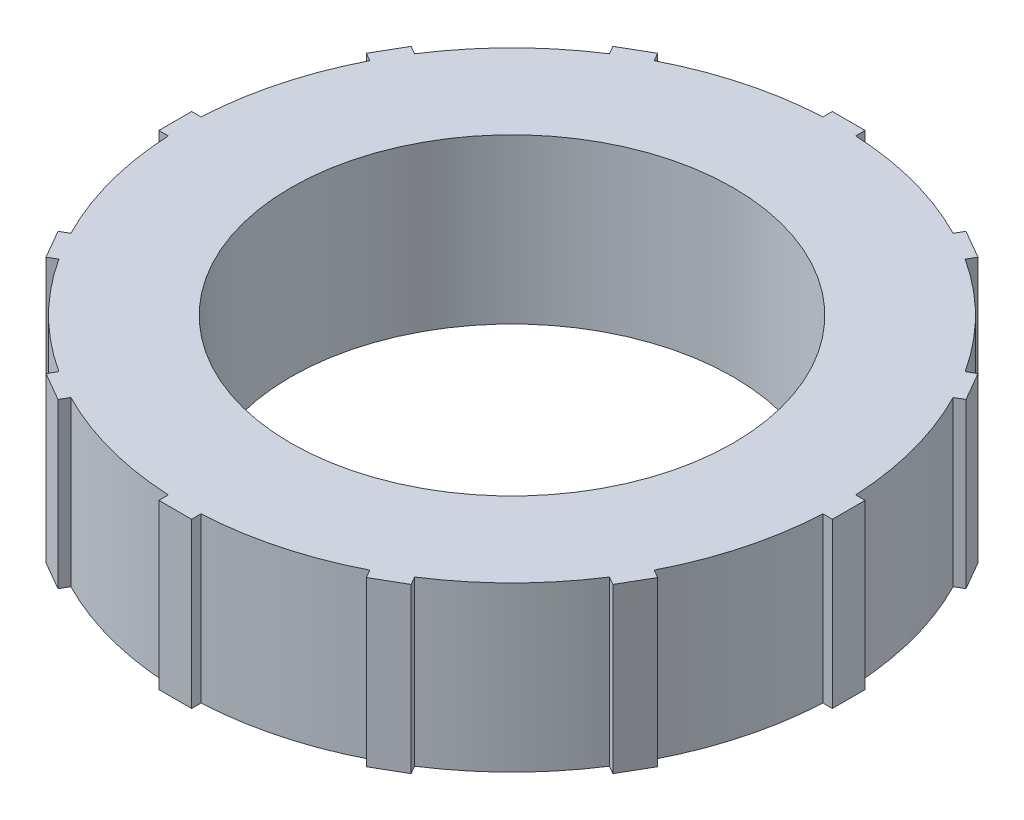
SolidWorks part; units mm, degrees
other "Ribbed TPU Tyre"
ref_plane "Front Plane" through (0, 0, 0) normal (0, 0, 1) x (1, 0, 0)
ref_plane "Top Plane" through (0, 0, 0) normal (0, 1, 0) x (1, 0, 0)
ref_plane "Right Plane" through (0, 0, 0) normal (1, 0, 0) x (0, 0, -1)
sketch3d "Tyre base sketch datum points"
  point P0 (-19.0092, -283, -53.2449)
  point P1 (-9.0092, -283, -53.2449)
  point P2 (-19.0092, -283, -63.2449)
ref_plane "Tyre base sketch plane" through (0, -283, 0) normal (0, 1, 0) x (1, 0, 0)
sketch "Tyre base sketch" plane through (0, -283, 0) normal (0, 1, 0) x (1, 0, 0)
  circle A0 centre (-19.0092, 53.2449) radius 40
extrude "Tyre base" add sketch "Tyre base sketch" along normal blind 20 separate body
sketch3d "Rim bore sketch datum points"
  point P0 (-19.0092, -283.1, -53.2449)
  point P1 (-9.0092, -283.1, -53.2449)
  point P2 (-19.0092, -283.1, -63.2449)
ref_plane "Rim bore sketch plane" through (0, -283.1, 0) normal (0, 1, 0) x (1, 0, 0)
sketch "Rim bore sketch" plane through (0, -283.1, 0) normal (0, 1, 0) x (1, 0, 0)
  circle A0 centre (-19.0092, 53.2449) radius 27
extrude "Rim bore" cut sketch "Rim bore sketch" along normal blind 20.2
sketch3d "Tread rib sketch datum points"
  point P0 (18.8908, -283, -55.2449)
  point P1 (28.8908, -283, -55.2449)
  point P2 (18.8908, -273, -55.2449)
ref_plane "Tread rib sketch plane" through (0, 0, -55.2449) normal (0, 0, 1) x (1, 0, 0)
sketch "Tread rib sketch" plane through (0, 0, -55.2449) normal (0, 0, 1) x (1, 0, 0)
  line L0 (18.8908, -283) -> (22.0908, -283)
  line L1 (22.0908, -283) -> (22.0908, -263)
  line L2 (22.0908, -263) -> (18.8908, -263)
  line L3 (18.8908, -263) -> (18.8908, -283)
extrude "Tread rib" add sketch "Tread rib sketch" along normal blind 4
sketch3d "CircularPattern1 axis line"
  line L0 (-19.0092, -10, -53.2449) -> (-19.0092, 10, -53.2449) construction
ref_axis "CircularPattern1 axis" through (-19.0092, -10, -53.2449) along (0, 1, 0)
pattern_circular "CircularPattern1" count 12 over 360 about axis through (-19.0092, -10, -53.2449) along (0, 1, 0) of "Tread rib"
